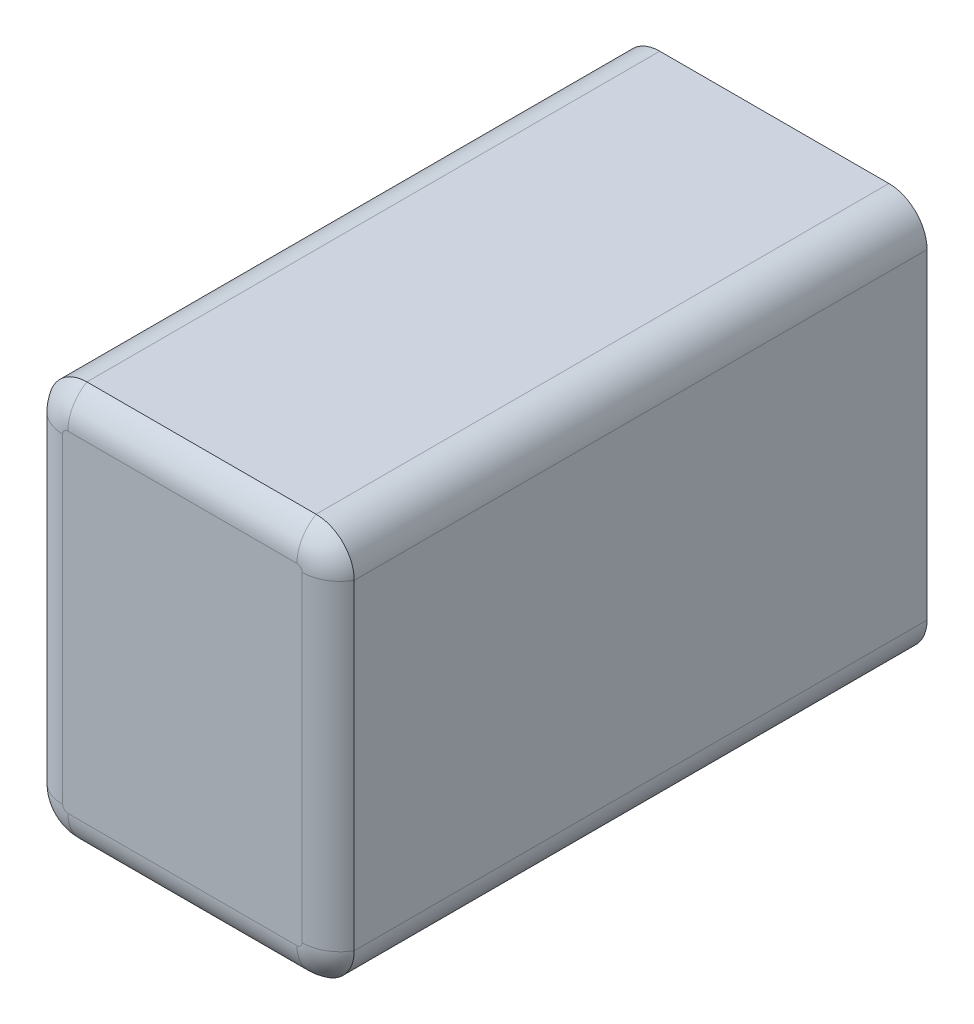
SolidWorks part; units mm, degrees
ref_plane "前基準面" through (0, 0, 0) normal (0, 0, 1) x (1, 0, 0)
ref_plane "上基準面" through (0, 0, 0) normal (0, 1, 0) x (1, 0, 0)
ref_plane "右基準面" through (0, 0, 0) normal (1, 0, 0) x (0, 0, -1)
sketch "草圖1" plane through (0, 0, 0) normal (0, 0, 1) x (1, 0, 0)
  line L0 (0, -55) -> (0, 55) construction
  line L5 (55, 0) -> (-55, 0) construction
  line L6 (-30, 52) -> (30, 52)
  line L7 (40, 42) -> (40, -42)
  line L8 (-30, -52) -> (30, -52)
  line L9 (-40, 42) -> (-40, -42)
  arc A0 (-30, 52) -> (-40, 42) centre (-30, 42) ccw
  arc A1 (30, 52) -> (40, 42) centre (30, 42) cw
  arc A2 (-30, -52) -> (-40, -42) centre (-30, -42) cw
  arc A3 (30, -52) -> (40, -42) centre (30, -42) ccw
  point P2 (-30.4023, 38.4874)
  dimension "D1" = 20
  dimension "D4" = 40
  dimension "D5" = 52
extrude "填料-伸長1" add sketch "草圖1" along normal blind 150
ref_plane "平面1" through (0, 0, 155) normal (0, 0, 1) x (1, 0, 0)
sketch "草圖3" plane through (0, 0, 150) normal (0, 0, 1) x (1, 0, 0)
  line L1 (-30, 52) -> (30, 52)
  line L2 (-40, 42) -> (-40, -42)
  line L3 (-30, -52) -> (30, -52)
  line L4 (40, 42) -> (40, -42)
  arc A0 (-40, 42) -> (-30, 52) centre (-30, 42) cw
  arc A1 (30, 52) -> (40, 42) centre (30, 42) cw
  arc A2 (-40, -42) -> (-30, -52) centre (-30, -42) ccw
  arc A3 (30, -52) -> (40, -42) centre (30, -42) ccw
extrude "填料-伸長3" add sketch "草圖3" along normal up to surface (5 mm away) draft 28
shell "薄殼9" thickness 2
fillet "圓角22" radius 10 8 edges at (-35.1912, -47.1912, 155) (-37.3415, 0, 155) (-35.1912, 47.1912, 155) (0, 49.3415, 155) (35.1912, 47.1912, 155) (37.3415, 0, 155) (35.1912, -47.1912, 155) (0, -49.3415, 155)
